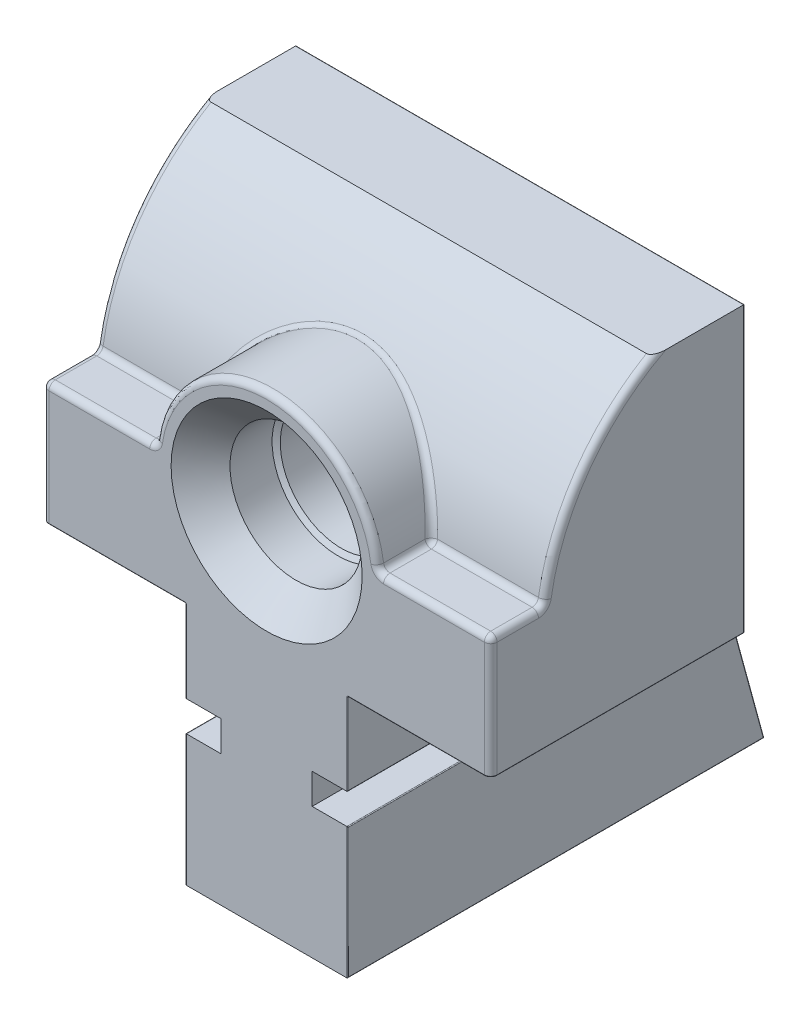
SolidWorks part; units mm, degrees
ref_plane "Front Plane" through (0, 0, 0) normal (0, 0, 1) x (1, 0, 0)
ref_plane "Top Plane" through (0, 0, 0) normal (0, 1, 0) x (1, 0, 0)
ref_plane "Right Plane" through (0, 0, 0) normal (1, 0, 0) x (0, 0, -1)
sketch "Sketch1" plane through (0, 0, 0) normal (0, 0, 1) x (1, 0, 0)
  line L0 (0, 0) -> (0, 57.9014) construction
  line L1 (12.6492, 0) -> (12.6492, 38.1)
  line L2 (12.6492, 38.1) -> (35.0012, 38.1)
  line L3 (35.0012, 38.1) -> (35.0012, 57.15)
  line L4 (-35.0012, 38.1) -> (-35.0012, 57.15)
  line L5 (-12.6492, 38.1) -> (-35.0012, 38.1)
  line L6 (-12.6492, 0) -> (-12.6492, 38.1)
  line L7 (-35.0012, 57.15) -> (35.0012, 57.15)
  line L8 (12.6492, 0) -> (-12.6492, 0)
  dimension "D1" = 38.1
  dimension "D2" = 22.352
  dimension "D3" = 19.05
  dimension "D4" = 25.2984
extrude "Boss-Extrude1" add sketch "Sketch1" against normal blind 65.0748
sketch "Sketch2" plane through (-35.0012, 0, 0) normal (-1, 0, 0) x (0, 0, 1)
  line L0 (-8.3272, 57.15) -> (-39.624, 57.15)
  line L1 (-65.0748, 57.15) -> (0, 57.15) construction
  line L2 (-39.624, 57.15) -> (-39.624, 82.55)
  line L3 (-39.624, 82.55) -> (-25.3198, 82.55)
  line L5 (0, 57.15) -> (0, 38.1) construction
  line L7 (-65.0748, 38.1) -> (0, 38.1) construction
  arc A0 (-25.3198, 82.55) -> (-8.3272, 57.15) centre (-42.926, 52.3875) cw
  dimension "D2" = 34.925
  dimension "D1" = 39.624
  dimension "D3" = 44.45
  dimension "D4" = 3.302
  dimension "D5" = 30.1625
extrude "Boss-Extrude2" add sketch "Sketch2" against normal up to surface (70.0024 mm away) up to face at (35.0012, 47.625, -32.5374)
sketch "Sketch3" plane through (-35.0012, 0, 0) normal (-1, 0, 0) x (0, 0, 1)
  line L0 (-39.624, 57.15) -> (-39.624, 34.925)
  line L1 (-39.624, 34.925) -> (-55.5498, 34.925)
  line L2 (-55.5498, 34.925) -> (-65.0748, 0)
  line L3 (-65.0748, 38.1) -> (-65.0748, 0) construction
  line L4 (-65.0748, 0) -> (0, 0) construction
  dimension "D1" = 9.525
  dimension "D2" = 34.925
extrude "Cut-Extrude1" cut sketch "Sketch3" against normal through all and the other way through all flip side to cut contours L0 L1 L2
sketch "Sketch4" plane through (0, 0, 0) normal (0, 0, 1) x (1, 0, 0)
  line L0 (0, 0) -> (0, 55.5498) construction
  line L1 (-17.4498, 55.5498) -> (17.4498, 55.5498)
  arc A0 (17.4498, 55.5498) -> (-17.4498, 55.5498) centre (0, 55.5498) ccw
  dimension "D2" = 34.8996
  dimension "D1" = 55.5498
extrude "Boss-Extrude4" add sketch "Sketch4" against normal up to surface (8.1445 mm away) contours A0 L1 up to face at (0, 70.8286, -15.3607)
sketch "Sketch5" plane through (0, 0, 0) normal (0, 0, 1) x (1, 0, 0)
  circle A0 centre (0, 55.5498) radius 9.525
  dimension "D1" = 19.05
extrude "Cut-Extrude2" cut sketch "Sketch5" against normal blind 30.1625 contours A0
hole_wizard "1-1/8-7 Tapped Hole1" positions "Sketch6" profile "Sketch7" tap size "1-1/8-7" standard "ANSI Inch"
sketch "Sketch6" plane through (0, 0, 0) normal (0, 0, 1) x (1, 0, 0)
  point P0 (0, 55.5498)
sketch "Sketch7" plane through (0, 55.5498, 0) normal (1, 0, 0) x (0, -1, 0)
  line L0 (0, 0) -> (0, 17.3799)
  line L1 (0, 17.3799) -> (10.3251, 11.176)
  line L2 (10.3251, 11.176) -> (10.3251, 4.5974)
  line L3 (10.3251, 4.5974) -> (14.9225, 0)
  line L5 (14.9225, 0) -> (0, 0)
  line L6 (-10.3251, 4.5974) -> (-14.9225, 0) construction
  line L10 (0, 17.3799) -> (-10.3251, 11.176) construction
  line L11 (0, -6.35) -> (0, 107.95) construction
  dimension "Tap Drill Dia." = 20.6502
  dimension "Tap Drill Depth" = 11.176
  dimension "Near C'Sink Dia." = 29.845
  dimension "Near C'Sink Angle" = 90
  dimension "Drill Angle" = 118
cosmetic thread "Hole Thread1" parameters "D1"=57.15, "D2"=28.575
sketch "Sketch8" plane through (0, 0, 0) normal (0, 0, 1) x (1, 0, 0)
  line L0 (0, 0) -> (0, 49.525) construction
  line L1 (12.6492, 0) -> (12.6492, 38.1) construction
  line L2 (12.6492, 25.2476) -> (7.112, 25.2476)
  line L3 (12.6492, 25.2476) -> (12.6492, 20.4978)
  line L4 (12.6492, 20.4978) -> (7.112, 20.4978)
  line L5 (7.112, 25.2476) -> (7.112, 20.4978)
  line L6 (12.6492, 38.1) -> (35.0012, 38.1) construction
  dimension "D1" = 5.5372
  dimension "D2" = 4.7498
  dimension "D3" = 12.8524
extrude "Cut-Extrude3" cut sketch "Sketch8" against normal through all
mirror "Mirror1" about plane through (0, 0, 0) normal (1, 0, 0) of "Cut-Extrude3"
hole_wizard "1/4-20 Tapped Hole1" positions "Sketch9" profile "Sketch10" tap size "1/4-20" standard "ANSI Inch"
sketch "Sketch9" plane through (0, 0, -39.624) normal (0, 0, -1) x (-1, 0, 0)
  line L0 (0, 82.55) -> (0, 38.6008) construction
  line L1 (-35.0012, 82.55) -> (35.0012, 82.55) construction
  line L2 (12.6492, 38.1) -> (35.0012, 38.1) construction
  point P0 (-19.05, 63.5)
  point P9 (19.05, 63.5)
  dimension "D1" = 38.1
  dimension "D2" = 25.4
sketch "Sketch10" plane through (19.05, 63.5, -39.624) normal (1, 0, 0) x (0, 1, 0)
  line L0 (0, 0) -> (0, 17.4088)
  line L1 (0, 17.4088) -> (2.5527, 15.875)
  line L2 (2.5527, 15.875) -> (2.5527, 1.2573)
  line L3 (2.5527, 1.2573) -> (3.81, 0)
  line L5 (3.81, 0) -> (0, 0)
  line L6 (-2.5527, 1.2573) -> (-3.81, 0) construction
  line L10 (0, 17.4088) -> (-2.5527, 15.875) construction
  line L11 (0, -6.35) -> (0, 107.95) construction
  dimension "Tap Drill Dia." = 5.1054
  dimension "Tap Drill Depth" = 15.875
  dimension "Near C'Sink Dia." = 7.62
  dimension "Near C'Sink Angle" = 90
  dimension "Drill Angle" = 118
cosmetic thread "Hole Thread2" parameters "D1"=12.7, "D2"=6.35
cosmetic thread "Hole Thread3" parameters "D1"=12.7, "D2"=6.35
fillet "Fillet9" radius 1 14 edges at (35.0012, 47.625, 0) (35.0012, 71.8072, -13.8979) (35.0012, 57.15, -4.1636) (17.3763, 57.15, -4.1636) (26.1887, 57.15, 0) (26.1887, 57.15, -8.3272) (-35.0012, 47.625, 0) (-35.0012, 71.8072, -13.8979) (-35.0012, 57.15, -4.1636) (-26.1887, 57.15, 0) (-26.1887, 57.15, -8.3272) (-2.098, 72.873, -14.64) (0, 72.9996, 0) (-17.3763, 57.15, -4.1636)
hole_wizard "#25 (0.1495) Diameter Hole1" positions "Sketch12" profile "Sketch13" hole size "#25" standard "ANSI Inch"
sketch "Sketch12" plane through (0, 0, 0) normal (0, -1, 0) x (-1, 0, 0)
  line L0 (0, 65.0748) -> (0, 0) construction
  line L1 (12.6492, 65.0748) -> (-12.6492, 65.0748) construction
  line L3 (12.6492, 0) -> (-12.6492, 0) construction
  point P0 (-7.9375, 30.1625)
  dimension "D1" = 30.1625
  dimension "D2" = 7.9375
sketch "Sketch13" plane through (7.9375, 0, -30.1625) normal (1, 0, 0) x (0, 0, -1)
  line L0 (0, 0) -> (0, 28.1283)
  line L1 (0, 28.1283) -> (1.8986, 26.9875)
  line L2 (1.8986, 26.9875) -> (1.8986, 0.635)
  line L3 (1.8986, 0.635) -> (2.5337, 0)
  line L5 (2.5337, 0) -> (0, 0)
  line L6 (-1.8986, 0.635) -> (-2.5337, 0) construction
  line L10 (0, 28.1283) -> (-1.8987, 26.9875) construction
  line L11 (0, -6.35) -> (0, 107.95) construction
  dimension "Hole Dia." = 3.7973
  dimension "Hole Depth" = 26.9875
  dimension "Near C'Sink Dia." = 5.0673
  dimension "Near C'Sink Angle" = 90
  dimension "Drill Angle" = 118
hole_wizard "1/4-28 Tapped Hole1" positions "Sketch14" profile "Sketch15" tap size "1/4-28" standard "ANSI Inch"
sketch "Sketch14" plane through (0, 0, 0) normal (0, -1, 0) x (-1, 0, 0)
  point P0 (-7.9375, 30.1625)
sketch "Sketch15" plane through (7.9375, 0, -30.1625) normal (1, 0, 0) x (0, 0, -1)
  line L0 (0, 0) -> (0, 20.6754)
  line L1 (0, 20.6754) -> (2.7051, 19.05)
  line L2 (2.7051, 19.05) -> (2.7051, 1.1049)
  line L3 (2.7051, 1.1049) -> (3.81, 0)
  line L5 (3.81, 0) -> (0, 0)
  line L6 (-2.7051, 1.1049) -> (-3.81, 0) construction
  line L10 (0, 20.6754) -> (-2.7051, 19.05) construction
  line L11 (0, -6.35) -> (0, 107.95) construction
  dimension "Tap Drill Dia." = 5.4102
  dimension "Tap Drill Depth" = 19.05
  dimension "Near C'Sink Dia." = 7.62
  dimension "Near C'Sink Angle" = 90
  dimension "Drill Angle" = 118
cosmetic thread "Hole Thread4" parameters "D1"=12.7, "D2"=6.35
hole_wizard "7/32 (0.21875) Diameter Hole1" positions "Sketch16" profile "Sketch17" hole size "7/32" standard "ANSI Inch"
sketch "Sketch16" plane through (0, 0, 0) normal (0, -1, 0) x (-1, 0, 0)
  point P0 (-7.9375, 30.1625)
sketch "Sketch17" plane through (7.9375, 0, -30.1625) normal (1, 0, 0) x (0, 0, -1)
  line L0 (0, 0) -> (0, 11.1943)
  line L1 (0, 11.1943) -> (2.7781, 9.525)
  line L2 (2.7781, 9.525) -> (2.7781, 0.635)
  line L3 (2.7781, 0.635) -> (3.4131, 0)
  line L5 (3.4131, 0) -> (0, 0)
  line L6 (-2.7781, 0.635) -> (-3.4131, 0) construction
  line L10 (0, 11.1943) -> (-2.7781, 9.525) construction
  line L11 (0, -6.35) -> (0, 107.95) construction
  dimension "Hole Dia." = 5.5562
  dimension "Hole Depth" = 9.525
  dimension "Near C'Sink Dia." = 6.8262
  dimension "Near C'Sink Angle" = 90
  dimension "Drill Angle" = 118
mirror "Mirror2" about plane through (0, 0, 0) normal (1, 0, 0) of "#25 (0.1495) Diameter Hole1", "1/4-28 Tapped Hole1", "7/32 (0.21875) Diameter Hole1"
cosmetic thread "Hole Thread5" parameters "D1"=12.7, "D2"=6.35
fillet "Fillet10" radius 0.127 34 edges at (-35.0012, 38.1, -20.312) (-34.7083, 38.1, -0.2929) (-23.3252, 38.1, 0) (-12.6492, 0, -32.5374) (-12.6492, 10.2489, -62.2796) (-12.6492, 20.4978, -29.7422) (-12.6492, 10.2489, 0) (-12.6492, 34.925, -47.5869) (-12.6492, 38.1, -19.812) (-12.6492, 31.6738, 0) (-12.6492, 25.2476, -29.0945) (-12.6492, 30.0863, -56.8694) (12.6492, 10.2489, -62.2796) (12.6492, 0, -32.5374) (12.6492, 10.2489, 0) (12.6492, 20.4978, -29.7422) (12.6492, 31.6738, 0) (12.6492, 34.925, -47.5869) (12.6492, 30.0863, -56.8694) (12.6492, 25.2476, -29.0945) (12.6492, 38.1, -19.812) (23.3252, 38.1, 0) (34.7083, 38.1, -0.2929) (35.0012, 38.1, -20.312) (-35.0012, 60.325, -39.624) (-23.8252, 38.1, -39.624) (-12.6492, 36.5125, -39.624) (0, 34.925, -39.624) (12.6492, 36.5125, -39.624) (23.8252, 38.1, -39.624) (35.0012, 60.325, -39.624) (0, 82.55, -39.624) (-22.86, 63.5, -39.624) (15.24, 63.5, -39.624)
